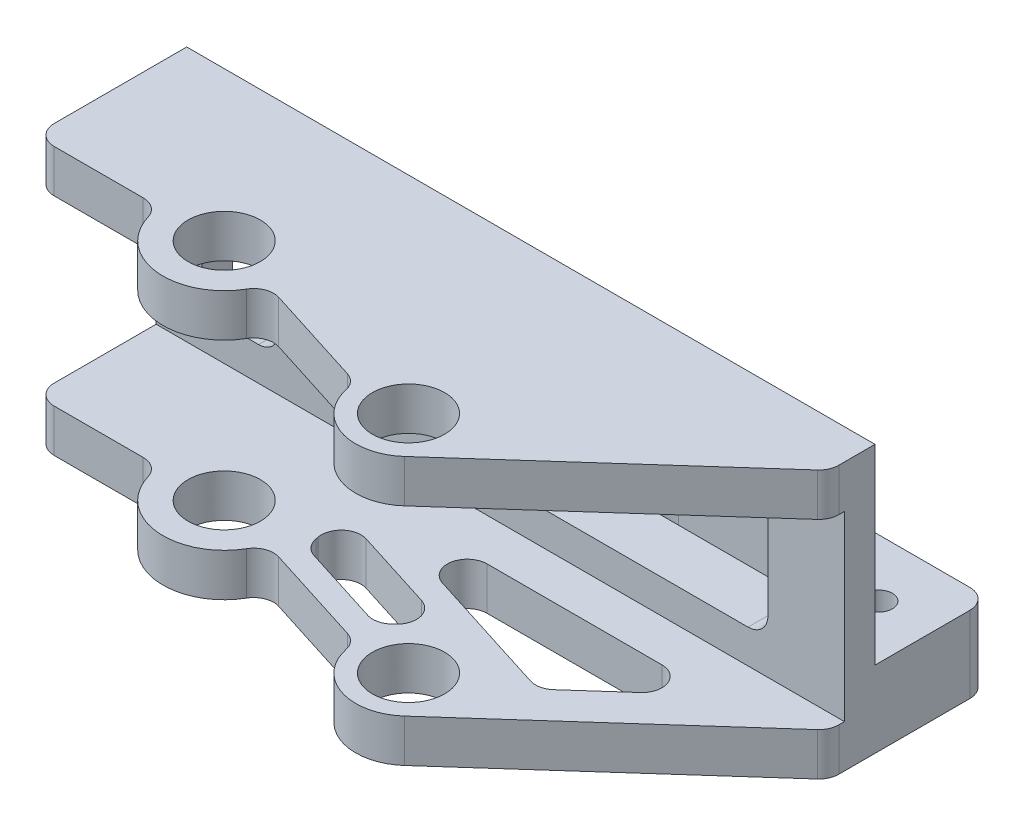
SolidWorks part; units mm, degrees
ref_plane "Front Plane" through (0, 0, 0) normal (0, 0, 1) x (1, 0, 0)
ref_plane "Top Plane" through (0, 0, 0) normal (0, 1, 0) x (1, 0, 0)
ref_plane "Right Plane" through (0, 0, 0) normal (1, 0, 0) x (0, 0, -1)
sketch "Sketch1" plane through (0, 0, 0) normal (0, 0, 1) x (1, 0, 0)
  line L1 (57.15, 22.225) -> (-57.15, 22.225)
  line L2 (57.15, 22.225) -> (57.15, -22.225)
  line L3 (57.15, -22.225) -> (-57.15, -22.225)
  line L4 (-57.15, 22.225) -> (-57.15, -22.225)
  line L5 (57.15, 22.225) -> (-57.15, -22.225) construction
  line L6 (57.15, -22.225) -> (-57.15, 22.225) construction
  point P0 (0, 0)
  dimension "D1" = 44.45
  dimension "D2" = 114.3
extrude "Boss-Extrude1" add sketch "Sketch1" along normal mid plane 62.23
sketch "Sketch3" plane through (0, -22.225, 0) normal (0, -1, 0) x (1, 0, 0)
  line L0 (57.15, -12.065) -> (-57.15, -12.065) construction
  line L1 (57.15, 31.115) -> (57.15, -31.115) construction
  line L2 (-57.15, 31.115) -> (-57.15, -31.115) construction
  line L3 (-57.15, -31.115) -> (57.15, -31.115) construction
  circle A0 centre (-26.162, 12.7) radius 6
  circle A1 centre (13.97, 22.225) radius 6
  dimension "D2" = 34.29
  dimension "D3" = 30.988
  dimension "D4" = 12
  dimension "D6" = 12
  dimension "D7" = 40.132
  dimension "D1" = 19.05
  dimension "D5" = 9.525
extrude "Pivot Points" cut sketch "Sketch3" against normal through all
sketch "Sketch4" plane through (0, 0, 31.115) normal (0, 0, 1) x (1, 0, 0)
  line L0 (57.15, -22.225) -> (57.15, 22.225) construction
  line L1 (-57.15, -15.113) -> (57.15, -15.113)
  line L2 (-57.15, -15.113) -> (-57.15, 15.113)
  line L3 (-57.15, 15.113) -> (57.15, 15.113)
  line L4 (57.15, -15.113) -> (57.15, 15.113)
  line L5 (-57.15, -15.113) -> (57.15, 15.113) construction
  line L6 (-57.15, 15.113) -> (57.15, -15.113) construction
  line L7 (57.15, 22.225) -> (-57.15, 22.225) construction
  point P0 (0, 0)
  dimension "D1" = 7.112
extrude "Top Cutout" cut sketch "Sketch4" against normal blind 38.1
sketch "Sketch5" plane through (0, 0, -31.115) normal (0, 0, -1) x (-1, 0, 0)
  line L0 (57.15, 22.225) -> (57.15, -22.225) construction
  line L1 (-57.15, 22.225) -> (57.15, 22.225)
  line L2 (-57.15, 22.225) -> (-57.15, -9.525)
  line L3 (-57.15, -9.525) -> (57.15, -9.525)
  line L4 (57.15, 22.225) -> (57.15, -9.525)
  line L5 (57.15, -22.225) -> (-57.15, -22.225) construction
  dimension "D1" = 12.7
extrude "Bottom Cutout" cut sketch "Sketch5" against normal blind 19.05
sketch "Sketch6" plane through (0, -22.225, 0) normal (0, -1, 0) x (1, 0, 0)
  line L0 (-16.3656, 15.3939) -> (5.207, 22.225)
  line L1 (19.8051, 28.7628) -> (57.15, -4.5682)
  line L2 (57.15, 31.115) -> (57.15, -31.115) construction
  line L3 (-36.3072, 13.2479) -> (-57.15, 13.2479)
  line L4 (-57.15, 31.115) -> (-57.15, -31.115) construction
  line L5 (-57.15, 13.2479) -> (-57.15, 31.115)
  line L6 (-57.15, 31.115) -> (57.15, 31.115)
  line L7 (57.15, 31.115) -> (57.15, -4.5682)
  line L8 (-57.15, -12.065) -> (-21.59, -12.065)
  line L9 (-21.59, -12.065) -> (-4.826, -31.115)
  line L10 (-57.15, -31.115) -> (57.15, -31.115) construction
  line L11 (-4.826, -31.115) -> (-57.15, -31.115)
  line L12 (-57.15, -31.115) -> (-57.15, -12.065)
  circle A0 centre (13.97, 22.225) radius 8.763 construction
  circle A1 centre (-26.162, 12.7) radius 10.16 construction
  arc A2 (5.207, 22.225) -> (19.8051, 28.7628) centre (13.97, 22.225) cw
  arc A3 (-36.3072, 13.2479) -> (-16.3656, 15.3939) centre (-26.162, 12.7) cw
  point P22 (57.15, -5.0532)
  point P28 (0, 0)
  point P29 (0, 0)
  point P30 (0, 0)
  point P31 (57.15, -13.752)
  point P32 (0, 0)
  point P33 (57.15, -6.2475)
  point P34 (57.15, -6.9138)
  point P35 (57.15, -4.5682)
  point P36 (-57.15, 13.2479)
  line M8 (-57.15, -31.115) -> (57.15, -31.115)
  line M9 (57.15, -31.115) -> (57.15, 31.115)
  line M10 (57.15, 31.115) -> (-57.15, 31.115)
  line M11 (-57.15, 31.115) -> (-57.15, -31.115)
  dimension "D1" = 8.763
  dimension "D2" = 20.32
  dimension "D8" = 8.763
  dimension "D3" = 35.56
  dimension "D4" = 52.324
  dimension "D5" = 19.05
  dimension "D6" = 22.6284
extrude "Side Profile Cut" cut sketch "Sketch6" against normal through all contours L3 A3 L0 A2 L1 M9 M10 M11 | L9 L8 M11 M8 region at (-27.3772, -22.225, 23.9922) region at (-34.9125, -22.225, -22.1956)
sketch "Sketch9" plane through (0, -22.225, 0) normal (0, -1, 0) x (-1, 0, 0)
  line L11 (-48.26, 21.59) -> (2.54, 21.59)
  line L13 (57.15, 12.065) -> (21.59, 12.065) construction
  line L14 (-57.15, 4.5682) -> (-57.15, 31.115) construction
  point P0 (2.54, 21.59)
  point P2 (-48.26, 21.59)
  dimension "D1" = 50.8
  dimension "D2" = 9.525
  dimension "D3" = 8.89
hole_wizard "#8 Clearance Hole1" positions "Sketch9" profile "Sketch8" hole size "#8" standard "ANSI Inch" end condition through all
sketch "Sketch8" plane through (-2.54, -22.225, -21.59) normal (1, 0, 0) x (0, 0, -1)
  line L0 (0, 0) -> (0, 44.45)
  line L1 (0, 44.45) -> (2.2479, 44.45)
  line L2 (2.2479, 44.45) -> (2.2479, 0)
  line L5 (2.2479, 0) -> (0, 0)
  line L11 (0, -6.35) -> (0, 107.95) construction
  dimension "Thru Hole Dia." = 4.4958
  dimension "Thru Hole Depth" = 44.45
sketch "Sketch10" plane through (0, -22.225, 0) normal (0, -1, 0) x (1, 0, 0)
  line L3 (2.54, -15.875) -> (43.18, -15.875)
  line L4 (43.18, -15.875) -> (35.3562, -24.765)
  line L5 (35.3562, -24.765) -> (10.3632, -24.765)
  line L6 (10.3632, -24.765) -> (2.54, -15.875)
  line L7 (-12.6174, 12.5843) -> (-14.1466, 4.7594)
  line L8 (-14.1466, 4.7594) -> (10.1491, 12.4527)
  line L9 (19.8051, 28.7628) -> (57.15, -4.5682) construction
  line L10 (-16.3656, 15.3939) -> (5.207, 22.225) construction
  line L11 (-16.5558, 0) -> (42.4953, 0)
  line L12 (42.4953, 0) -> (27.0311, 13.802)
  line L13 (27.0311, 13.802) -> (-16.5558, 0)
  line L14 (10.1491, 12.4527) -> (4.0782, 17.8711)
  line L15 (4.0782, 17.8711) -> (-12.6174, 12.5843)
  line L16 (-21.59, -12.065) -> (-4.826, -31.115) construction
  line L17 (-4.826, -31.115) -> (57.15, -31.115) construction
  line L18 (-2.54, -21.59) -> (48.26, -21.59) construction
  line L19 (-57.15, -12.065) -> (-21.59, -12.065) construction
  circle A0 centre (-2.54, -21.59) radius 2.2479 construction
  circle A1 centre (48.26, -21.59) radius 2.2479 construction
  point P20 (22.86, -21.59)
  point P21 (22.86, -15.875)
  dimension "D1" = 3.81
  dimension "D2" = 180
  dimension "D3" = 3.81
  dimension "D4" = 45.72
  dimension "D5" = 131.348
  dimension "D6" = 131.35
  dimension "D7" = 6.35
  dimension "D8" = 40.64
  dimension "D9" = 3.81
  dimension "D10" = 6.35
extrude "optimization cutouts" cut sketch "Sketch10" along direction (0, -1, 0) on the side against the normal up to next (12.7 mm away)
sketch "Sketch12" plane through (0, 0, -6.985) normal (0, 0, 1) x (1, 0, 0)
  line L0 (57.15, 15.113) -> (-57.15, 15.113) construction
  line L1 (44.45, 15.113) -> (-6.35, 15.113)
  line L2 (44.45, 15.113) -> (44.45, -9.525)
  line L3 (44.45, -9.525) -> (-6.35, -9.525)
  line L4 (-6.35, 15.113) -> (-6.35, -9.525)
  line L5 (-57.15, 15.113) -> (-57.15, -15.113) construction
  line L6 (-36.83, -9.525) -> (-49.53, -9.525)
  line L7 (-36.83, -9.525) -> (-36.83, 15.113)
  line L8 (-36.83, 15.113) -> (-49.53, 15.113)
  line L9 (-49.53, -9.525) -> (-49.53, 15.113)
  line L10 (57.15, -15.113) -> (57.15, 15.113) construction
  line L12 (2.54, -9.525) -> (43.18, -9.525) construction
  dimension "D1" = 50.8
  dimension ".3" = 7.62
  dimension "D2" = 12.7
  dimension "D4" = 12.7
extrude "Cut-Extrude7" cut sketch "Sketch12" against normal through all
fillet "Fillet2" radius 3.302 30 edges at (57.15, 18.669, -4.5682) (5.207, 18.669, 22.225) (5.207, -18.669, 22.225) (57.15, -18.669, -4.5682) (57.15, -15.875, -31.115) (-4.826, -15.875, -31.115) (-21.59, -15.875, -12.065) (-16.5558, -18.669, 0) (42.4953, -18.669, 0) (27.0311, -18.669, 13.802) (35.3562, -15.875, -24.765) (43.18, -15.875, -15.875) (2.54, -15.875, -15.875) (10.3632, -15.875, -24.765) (-16.3656, -18.669, 15.3939) (-16.3656, 18.669, 15.3939) (-36.3072, 18.669, 13.2479) (-36.3072, -18.669, 13.2479) (-57.15, 18.669, 13.2479) (-57.15, -18.669, 13.2479) (44.45, -9.525, -9.525) (-36.83, -9.525, -9.525) (44.45, 15.113, -9.525) (-36.83, 15.113, -9.525) (-49.53, 15.113, -9.525) (-49.53, -9.525, -9.525) (10.1491, -18.669, 12.4527) (4.0782, -18.669, 17.8711) (-12.6174, -18.669, 12.5843) (-14.1466, -18.669, 4.7594)
sketch "Sketch15" plane through (0, 0, -6.985) normal (0, 0, 1) x (1, 0, 0)
  line L0 (-16.891, 5.3975) -> (-16.891, -5.3975)
  line L1 (-23.241, 15.113) -> (-23.241, -15.113) construction
  line L2 (-6.35, 15.113) -> (-40.132, 15.113) construction
  line L4 (-23.241, 0) -> (-16.891, 0) construction
  line L6 (-57.15, -15.113) -> (57.15, -15.113) construction
  point P0 (-16.891, 5.3975)
  point P2 (-16.891, -5.3975)
  dimension "D1" = 10.795
  dimension "D2" = 6.35
hole_wizard "#6 Clearance Hole1" positions "Sketch15" profile "Sketch14" hole size "#6" standard "ANSI Inch"
sketch "Sketch14" plane through (-16.891, 5.3975, -6.985) normal (1, 0, 0) x (0, -1, 0)
  line L0 (0, 0) -> (0, 10.7928)
  line L1 (0, 10.7928) -> (1.8986, 9.652)
  line L2 (1.8986, 9.652) -> (1.8986, 0)
  line L5 (1.8986, 0) -> (0, 0)
  line L10 (0, 10.7928) -> (-1.8987, 9.652) construction
  line L11 (0, -6.35) -> (0, 107.95) construction
  dimension "Hole Dia." = 3.7973
  dimension "Hole Depth" = 9.652
  dimension "Drill Angle" = 118
sketch "Sketch18" plane through (0, 0, -12.065) normal (0, 0, -1) x (-1, 0, 0)
  line L0 (57.15, -22.225) -> (57.15, 22.225) construction
  line L1 (-57.15, -9.525) -> (57.15, -9.525)
  line L2 (-57.15, -9.525) -> (-57.15, 9.525)
  line L3 (-57.15, 9.525) -> (57.15, 9.525)
  line L4 (57.15, -9.525) -> (57.15, 9.525)
  dimension "D1" = 19.05
split line "Split Line1"
